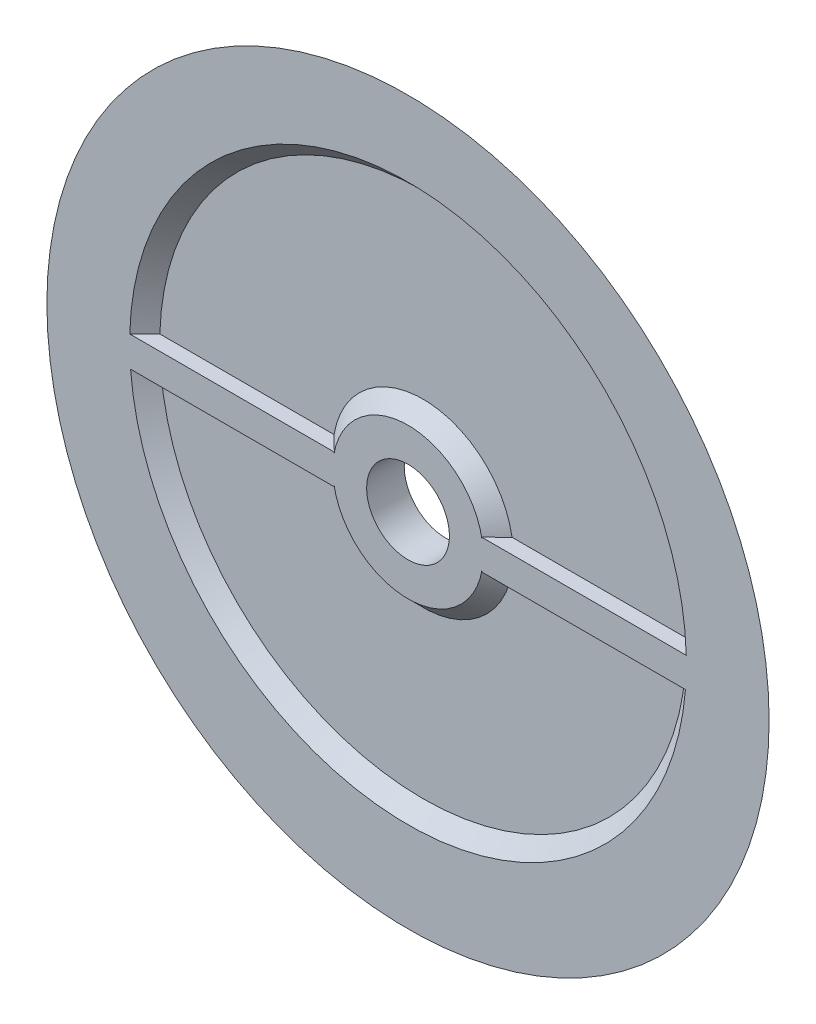
SolidWorks part; units mm, degrees
material "아크릴(내충격성)"
ref_plane "정면" through (0, 0, 0) normal (0, 0, 1) x (1, 0, 0)
ref_plane "윗면" through (0, 0, 0) normal (0, 1, 0) x (1, 0, 0)
ref_plane "우측면" through (0, 0, 0) normal (1, 0, 0) x (0, 0, -1)
sketch "스케치1" plane through (0, 0, 0) normal (0, 0, 1) x (1, 0, 0)
  circle A0 centre (0, 0) radius 37
  dimension "D1" = 74
extrude "보스-돌출1" add sketch "스케치1" along normal blind 5
ref_plane "평면1" through (0, 0, 2.5) normal (0, 0, 1) x (1, 0, 0)
sketch "스케치3" plane through (0, 0, 0) normal (0, 1, 0) x (1, 0, 0)
  line L0 (-37, -5) -> (-37, 0)
  line L1 (-37, 0) -> (-48, -5)
  line L2 (-48, -5) -> (-37, -5)
  line L3 (0, 6.4626) -> (0, -29.948) construction
  dimension "D1" = 11
revolve "회전1" add sketch "스케치3" angle 360 about L3
sketch "스케치4" plane through (0, 0, 0) normal (0, 0, -1) x (-1, 0, 0)
  circle A0 centre (0, 0) radius 34.4
  circle A1 centre (0, 0) radius 30.4
  circle A2 centre (0, 0) radius 37 construction
  dimension "D1" = 4
  dimension "D2" = 2.6
extrude "보스-돌출2" add sketch "스케치4" along normal blind 0.8
sketch "스케치5" plane through (0, 0, 0) normal (0, 0, -1) x (-1, 0, 0)
  circle A0 centre (0, 0) radius 5.5
  dimension "D1" = 11
extrude "컷-돌출1" cut sketch "스케치5" against normal through all contours A0
sketch "스케치6" plane through (0, 0, 5) normal (0, 0, 1) x (1, 0, 0)
  circle A0 centre (0, 0) radius 10
  circle A1 centre (0, 0.9905) radius 37
  dimension "D1" = 74
  dimension "D2" = 20
extrude "컷-돌출2" cut sketch "스케치6" against normal blind 2 draft 45
sketch "스케치7" plane through (0, 0, 5) normal (0, 0, 1) x (1, 0, 0)
  line L1 (-40.1871, 2) -> (-14.8661, 2)
  line L2 (-40.1871, 2) -> (-40.1871, -2)
  line L3 (-40.1871, -2) -> (-14.8661, -2)
  line L4 (-14.8661, 2) -> (-14.8661, -2)
  line L5 (-40.1871, 2) -> (-14.8661, -2) construction
  line L6 (-40.1871, -2) -> (-14.8661, 2) construction
  circle A1 centre (0, 0) radius 15 construction
  point P0 (-27.5266, 0)
  dimension "D1" = 4
extrude "보스-돌출3" add sketch "스케치7" against normal blind 2
sketch "스케치9" plane through (-14.8661, 0, 0) normal (1, 0, 0) x (0, 0, -1)
  line L1 (-5, 2) -> (-3, 2)
  line L2 (-5, 2) -> (-5, -2)
  line L3 (-5, -2) -> (-3, -2)
  line L4 (-3, 2) -> (-3, -2)
extrude "보스-돌출5" add sketch "스케치9" along normal blind 5
sketch "스케치10" plane through (0, 0, 0) normal (1, 0, 0) x (0, 0, -1)
  line L0 (37.3425, 0) -> (-26.3325, 0) construction
pattern_circular "원형 패턴1" count 2 over 360 about axis through (0, 0, -37.3425) along (0, 0, 1) of "보스-돌출3", "보스-돌출5"
